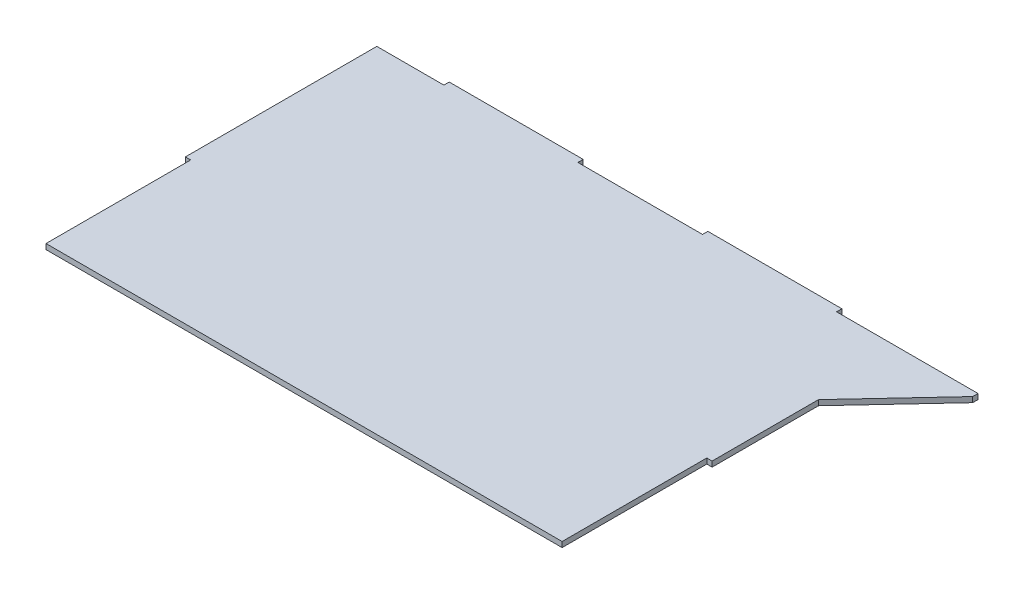
SolidWorks part; units mm, degrees
material "6061-T6 (SS)"
ref_plane "X-Y Datum" through (0, 0, 0) normal (0, 0, 1) x (1, 0, 0)
ref_plane "X-Z Datum" through (0, 0, 0) normal (0, 1, 0) x (1, 0, 0)
ref_plane "Y-Z Datum" through (0, 0, 0) normal (1, 0, 0) x (0, 0, -1)
sketch "Sketch1" plane through (0, 0, 0) normal (0, 0, 1) x (1, 0, 0)
  line L1 (-157.2306, -1.5875) -> (157.2306, -1.5875)
  line L2 (-157.2306, -1.5875) -> (-157.2306, 1.5875)
  line L3 (-157.2306, 1.5875) -> (157.2306, 1.5875)
  line L4 (157.2306, -1.5875) -> (157.2306, 1.5875)
  line L5 (-157.2306, -1.5875) -> (157.2306, 1.5875) construction
  line L6 (-157.2306, 1.5875) -> (157.2306, -1.5875) construction
  point P0 (0, 0)
  dimension "D1" = 314.4612
  dimension "D2" = 3.175
extrude "Boss-Extrude1" add sketch "Sketch1" along normal blind 200.6618
sketch "Sketch3" plane through (0, 0, 0) normal (0, 0, -1) x (-1, 0, 0)
  line L0 (-157.2306, 0) -> (-77.2306, 0) construction
  line L1 (-157.2306, -1.5875) -> (-157.2306, 1.5875) construction
  line L2 (-157.2306, 1.5875) -> (157.2306, 1.5875) construction
  line L3 (-117.2306, -1.5875) -> (-37.2306, -1.5875)
  line L4 (-117.2306, -1.5875) -> (-117.2306, 1.5875)
  line L5 (-117.2306, 1.5875) -> (-37.2306, 1.5875)
  line L6 (-37.2306, -1.5875) -> (-37.2306, 1.5875)
  line L7 (-117.2306, -1.5875) -> (-37.2306, 1.5875) construction
  line L8 (-117.2306, 1.5875) -> (-37.2306, -1.5875) construction
  line L14 (-157.2306, 1.5875) -> (-117.2306, 1.5875)
  line L15 (-157.2306, 1.5875) -> (-157.2306, -1.5875)
  line L16 (-157.2306, -1.5875) -> (-117.2306, -1.5875)
  line L17 (-117.2306, 1.5875) -> (-117.2306, -1.5875)
  line L19 (-37.2306, 1.5875) -> (-37.2306, -1.5875)
  line M3 (-157.2306, -1.5875) -> (157.2306, -1.5875)
  line M5 (157.2306, 1.5875) -> (-157.2306, 1.5875)
  dimension "D1" = 40
  dimension "D2" = 80
sketch "Sketch5" plane through (0, 1.5875, 0) normal (0, 1, 0) x (1, 0, 0)
  line L1 (-157.2306, -200.6618) -> (-154.0556, -200.6618)
  line L3 (-157.2306, -200.6618) -> (-157.2306, -114.3018)
  line L5 (-157.2306, -114.3018) -> (-154.0556, -114.3018)
  line L6 (-154.0556, -200.6618) -> (-154.0556, -114.3018)
  line M11 (-157.2306, 0) -> (-157.2306, -200.6618)
  line M12 (-157.2306, -200.6618) -> (157.2306, -200.6618)
  dimension "D1" = 86.36
  dimension "D2" = 3.175
extrude "Cut-Extrude2" cut sketch "Sketch5" against normal blind 3.175 and the other way through all contours M12 M11 region at (-155.6431, 1.5875, 157.4818)
mirror "Mirror1" about plane through (0, 0, 0) normal (1, 0, 0) of "Cut-Extrude2"
sketch "Sketch6" plane through (0, 1.5875, 0) normal (0, 1, 0) x (1, 0, 0)
  line L6 (-157.2306, -180.3418) -> (-81.0306, -180.3418)
  line L7 (-157.2306, -180.3418) -> (-157.2306, -200.6618)
  line L8 (-157.2306, -200.6618) -> (-81.0306, -200.6618)
  line L9 (-81.0306, -180.3418) -> (-81.0306, -200.6618)
  line L10 (154.0556, -200.6618) -> (-154.0556, -200.6618) construction
  line L11 (-157.2306, -114.3018) -> (-157.2306, 0) construction
  line L13 (154.0556, -200.6618) -> (-81.0306, -200.6618)
  line L14 (154.0556, -200.6618) -> (154.0556, -180.3418)
  line L15 (154.0556, -180.3418) -> (-81.0306, -180.3418)
  line L16 (-81.0306, -200.6618) -> (-81.0306, -180.3418)
  line M18 (-154.0556, -114.3018) -> (-154.0556, -200.6618)
  line M19 (-154.0556, -200.6618) -> (154.0556, -200.6618)
  dimension "D1" = 76.2
  dimension "D2" = 20.32
extrude "Cut-Extrude4" [suppressed] cut sketch "Sketch6" against normal through all contours L9 L6 M18 M19
sketch "Sketch7" [suppressed] plane through (0, 1.5875, 0) normal (0, 1, 0) x (1, 0, 0)
  line L1 (-81.2823, -215.455) -> (155.1963, -215.455)
  line L2 (-81.2823, -215.455) -> (-81.2823, -235.775)
  line L3 (-81.2823, -235.775) -> (155.1963, -235.775)
  line L4 (155.1963, -215.455) -> (155.1963, -235.775)
extrude "Cut-Extrude5" [suppressed] cut sketch "Sketch7" against normal through all
sketch "Sketch8" [suppressed] plane through (0, 1.5875, 0) normal (0, 1, 0) x (1, 0, 0)
  line L0 (155.1963, -235.775) -> (-155.1963, -235.775) construction
  line L1 (157.4823, -215.455) -> (81.2823, -215.455)
  line L2 (157.4823, -215.455) -> (157.4823, -235.775)
  line L3 (157.4823, -235.775) -> (81.2823, -235.775)
  line L4 (81.2823, -215.455) -> (81.2823, -235.775)
  line L5 (157.4823, -117.411) -> (157.4823, -3.175) construction
  dimension "D1" = 20.32
  dimension "D2" = 76.2
extrude "Cut-Extrude6" [suppressed] cut sketch "Sketch8" against normal through all
sketch "Sketch9" [suppressed] plane through (0, 0, 215.455) normal (0, 0, 1) x (1, 0, 0)
  line L4 (155.1963, 1.5875) -> (-155.1963, 1.5875)
  line L5 (-155.1963, 1.5875) -> (-155.1963, -1.5875)
  line L6 (-155.1963, -1.5875) -> (155.1963, -1.5875)
  line L7 (155.1963, -1.5875) -> (155.1963, 1.5875)
  line L8 (155.1963, 1.5875) -> (-155.1963, 1.5875)
  line L9 (-155.1963, 1.5875) -> (-155.1963, -1.5875)
  line L10 (-155.1963, -1.5875) -> (155.1963, -1.5875)
  line L11 (155.1963, -1.5875) -> (155.1963, 1.5875)
  dimension "D1" = 0
extrude "Cut-Extrude7" [suppressed] cut sketch "Sketch9" against normal blind 11.68
extrude "Boss-Extrude2" add sketch "Sketch3" along normal blind 3.175 contours L6 L4 M3 M5 region at (77.2306, 0, 0)
pattern_linear "LPattern2" count 2 spacing 154.43 along (-1, 0, 0) of "Boss-Extrude2"
sketch "Sketch10" plane through (0, -1.5875, 0) normal (0, -1, 0) x (1, 0, 0)
  line L2 (201.6654, 0) -> (201.6654, 3.175)
  line L6 (157.2306, 50.8) -> (201.6654, 3.175)
  line L8 (157.2306, 0) -> (201.6654, 0)
  line L10 (157.2306, 114.3018) -> (157.2306, 0) construction
  line L11 (157.2306, 50.8) -> (157.2306, 0)
  dimension "D1" = 50.8
  dimension "D2" = 44.4348
  dimension "D3" = 3.175
extrude "Boss-Extrude3" add sketch "Sketch10" against normal blind 3.175
sketch "Sketch11" [suppressed] plane through (0, 0, 0) normal (0, 0, -1) x (-1, 0, 0)
  line L1 (37.2652, -1.5875) -> (117.2652, -1.5875)
  line L2 (37.2652, -1.5875) -> (37.2652, 1.5875)
  line L3 (37.2652, 1.5875) -> (117.2652, 1.5875)
  line L4 (117.2652, -1.5875) -> (117.2652, 1.5875)
  line L5 (-117.1668, -1.5875) -> (-37.1668, -1.5875)
  line L6 (-117.1668, -1.5875) -> (-117.1668, 1.5875)
  line L7 (-117.1668, 1.5875) -> (-37.1668, 1.5875)
  line L8 (-37.1668, -1.5875) -> (-37.1668, 1.5875)
extrude "Boss-Extrude4" [suppressed] add sketch "Sketch11" along normal blind 3.175
